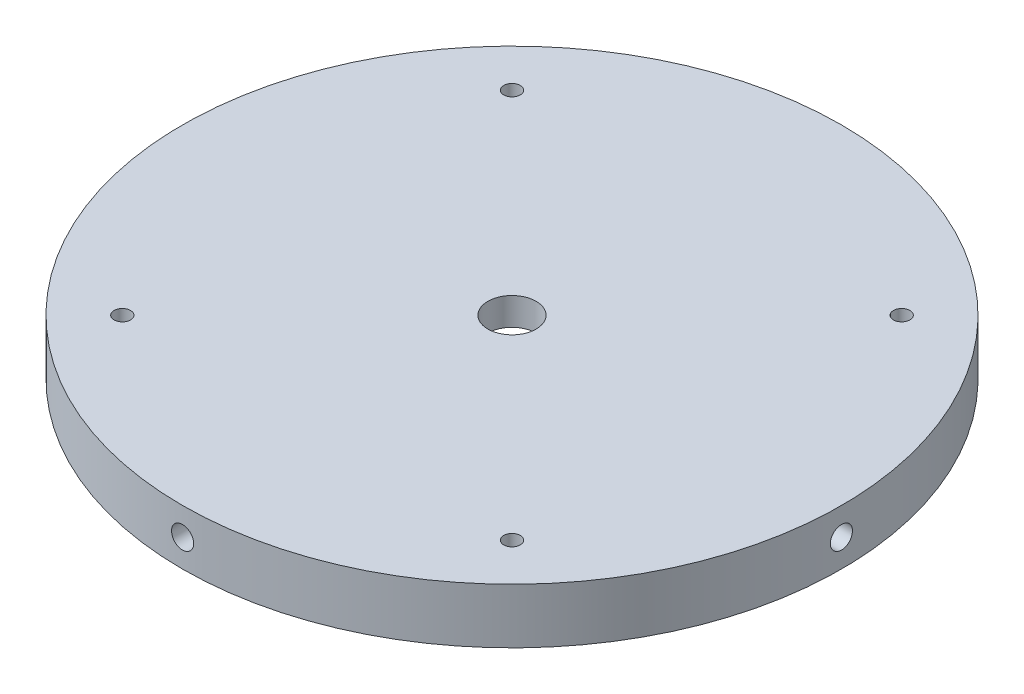
SolidWorks part; units mm, degrees
material "6061-T6 (SS)"
ref_plane "Front Plane" through (0, 0, 0) normal (0, 0, 1) x (1, 0, 0)
ref_plane "Top Plane" through (0, 0, 0) normal (0, 1, 0) x (1, 0, 0)
ref_plane "Right Plane" through (0, 0, 0) normal (1, 0, 0) x (0, 0, -1)
sketch "Sketch2" plane through (0, 0, 0) normal (0, 1, 0) x (1, 0, 0)
  circle A0 centre (0, 0) radius 75.946
  dimension "D1" = 151.892
extrude "Boss-Extrude1" add sketch "Sketch2" along normal blind 12.7
sketch "Sketch3" plane through (0, 12.7, 0) normal (0, 1, 0) x (1, 0, 0)
  circle A0 centre (0, 0) radius 5.5562
  dimension "D1" = 11.1125
extrude "Cut-Extrude1" cut sketch "Sketch3" against normal through all both and the other way through all
ref_plane "Plane2" through (0, 6.35, 0) normal (0, 1, 0) x (1, 0, 0)
sketch "Sketch7" plane through (0, 6.35, 0) normal (0, 1, 0) x (1, 0, 0)
  line L0 (-76.1746, 0) -> (76.1746, 0) construction
  line L1 (0, -76.1746) -> (0, 76.1746) construction
  circle A0 centre (0, 0) radius 76.1746 construction
  point P5 (-76.1746, 0)
  point P6 (0, 0)
  point P9 (0, 0)
ref_plane "Plane3" through (-76.1746, 0, 0) normal (1, 0, 0) x (0, 0, -1)
sketch "Sketch9" plane through (-76.1746, 0, 0) normal (1, 0, 0) x (0, 0, -1)
  point P0 (0, 6.35)
hole_wizard "1/4-20 Tapped Hole1" positions "Sketch9" profile "Sketch10" tap size "1/4-20" standard "ANSI Inch"
sketch "Sketch10" plane through (-76.1746, 6.35, 0) normal (0, 1, 0) x (0, 0, 1)
  line L0 (0, 0) -> (0, 26.9338)
  line L1 (0, 26.9338) -> (2.5527, 25.4)
  line L2 (2.5527, 25.4) -> (2.5527, 0)
  line L5 (2.5527, 0) -> (0, 0)
  line L10 (0, 26.9338) -> (-2.5527, 25.4) construction
  line L11 (0, -6.35) -> (0, 107.95) construction
  dimension "Tap Drill Dia." = 5.1054
  dimension "Tap Drill Depth" = 25.4
  dimension "Drill Angle" = 118
cosmetic thread "Hole Thread1" parameters "D1"=12.7, "D2"=6.1054
pattern_circular "CirPattern2" count 4 over 270 about axis through (0, 12.7, 0) along (0, -1, 0) of "1/4-20 Tapped Hole1"
sketch "Sketch11" plane through (0, 0, 0) normal (0, -1, 0) x (1, 0, 0)
  circle A0 centre (0, 0) radius 69.596
  circle A1 centre (0, 0) radius 75.946 construction
  dimension "D1" = 6.35
extrude "Cut-Extrude2" cut sketch "Sketch11" against normal offset from surface (6.35 mm away) 6.35 up to face at (0, 12.7, 5.5562)
split line "Split Line4"
sketch "Sketch11<2>" plane through (0, 0, 0) normal (0, -1, 0) x (1, 0, 0) same geometry as "Sketch11"
split line "Split Line5"
sketch "Sketch11<3>" plane through (0, 0, 0) normal (0, -1, 0) x (1, 0, 0) same geometry as "Sketch11"
sketch "Sketch12" plane through (0, 12.7, 0) normal (0, 1, 0) x (1, 0, 0)
  line L0 (0, 0) -> (63.5, 0) construction
  line L1 (0, 0) -> (44.9013, 44.9013) construction
  line L2 (0, 0) -> (44.9013, -44.9013) construction
  line L3 (0, 0) -> (-44.9013, -44.9013) construction
  line L4 (0, 0) -> (-44.9013, 44.9013) construction
  point P4 (44.9013, 44.9013)
  point P7 (44.9013, -44.9013)
  point P8 (-44.9013, -44.9013)
  point P9 (-44.9013, 44.9013)
  point P10 (0, 0)
  dimension "D1" = 63.5
  dimension "D2" = 45
  dimension "D3" = 4
hole_wizard "#10-24 Tapped Hole1" positions "Sketch12" profile "Sketch14" tap size "#10-24" standard "ANSI Inch"
sketch "Sketch14" plane through (0, 12.7, 0) normal (1, 0, 0) x (0, 0, 1)
  line L0 (0, 0) -> (0, 13.9704)
  line L1 (0, 13.9704) -> (1.8986, 12.8295)
  line L2 (1.8986, 12.8295) -> (1.8986, 0)
  line L5 (1.8986, 0) -> (0, 0)
  line L10 (0, 13.9704) -> (-1.8987, 12.8295) construction
  line L11 (0, -6.35) -> (0, 107.95) construction
  dimension "Tap Drill Dia." = 3.7973
  dimension "Tap Drill Depth" = 12.8295
  dimension "Drill Angle" = 118
cosmetic thread "Hole Thread2" parameters "D1"=9.652, "D2"=4.826
cosmetic thread "Hole Thread3" parameters "D1"=9.652, "D2"=4.826
cosmetic thread "Hole Thread4" parameters "D1"=9.652, "D2"=4.826
cosmetic thread "Hole Thread5" parameters "D1"=9.652, "D2"=4.826
